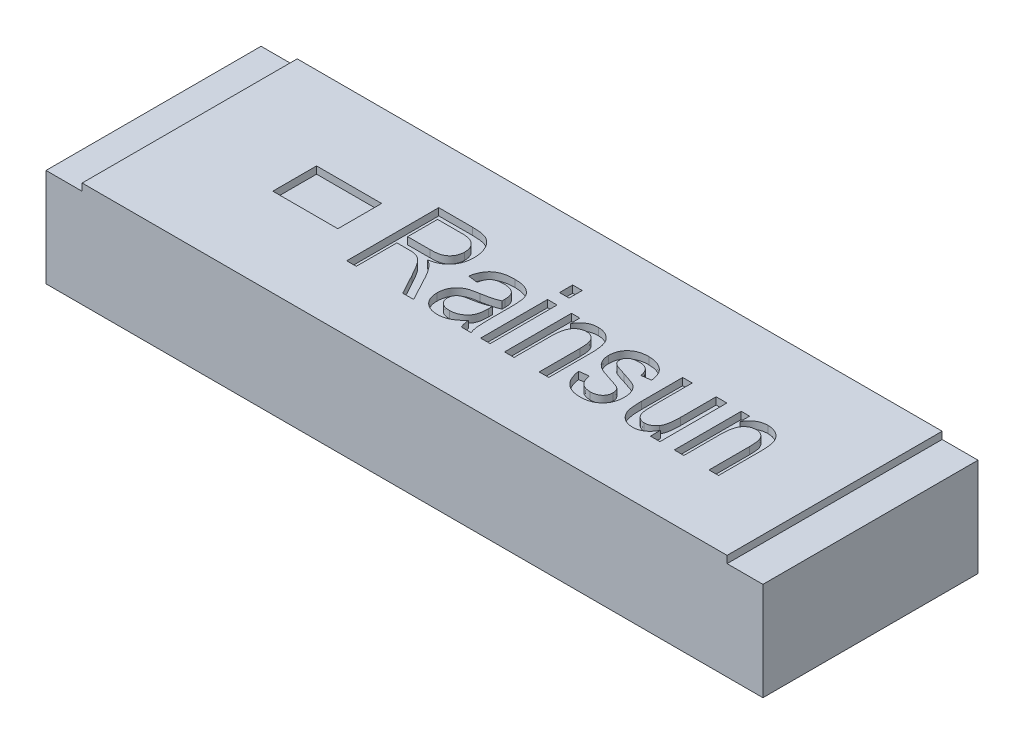
SolidWorks part; units mm, degrees
material "Plastique personnalisé"
ref_plane "Plan de face" through (0, 0, 0) normal (0, 0, 1) x (1, 0, 0)
ref_plane "Plan de dessus" through (0, 0, 0) normal (0, 1, 0) x (1, 0, 0)
ref_plane "Plan de droite" through (0, 0, 0) normal (1, 0, 0) x (0, 0, -1)
sketch "Esquisse1" plane through (0, 0, 0) normal (0, 1, 0) x (1, 0, 0)
  line L1 (-5, -1.5) -> (5, -1.5)
  line L2 (-5, -1.5) -> (-5, 1.5)
  line L3 (-5, 1.5) -> (5, 1.5)
  line L4 (5, -1.5) -> (5, 1.5)
  line L5 (-5, -1.5) -> (5, 1.5) construction
  line L6 (-5, 1.5) -> (5, -1.5) construction
  point P0 (0, 0)
  dimension "D1" = 10
  dimension "D2" = 3
extrude "Boss.-Extru.1" add sketch "Esquisse1" along normal blind 1.47
sketch "Esquisse2" plane through (0, 1.47, 0) normal (0, 1, 0) x (1, 0, 0)
  line L0 (0, 0) -> (-2.6139, 0.0364) construction
  line L2 (-3.0676, -0.2688) -> (-2.1603, -0.2688)
  line L3 (-3.0676, -0.2688) -> (-3.0676, 0.3417)
  line L4 (-3.0676, 0.3417) -> (-2.1603, 0.3417)
  line L5 (-2.1603, -0.2688) -> (-2.1603, 0.3417)
  line L6 (-3.0676, -0.2688) -> (-2.1603, 0.3417) construction
  line L7 (-3.0676, 0.3417) -> (-2.1603, -0.2688) construction
extrude "Enlèv. mat.-Extru.1" cut sketch "Esquisse2" against normal blind 0.1
sketch "Esquisse3" plane through (0, 1.47, 0) normal (0, 1, 0) x (1, 0, 0)
  line L0 (-5, -1.5) -> (5, -1.5) construction
  line L1 (-5, 1.5) -> (-4.4957, 1.5)
  line L2 (-5, 1.5) -> (-5, -1.5)
  line L3 (-5, -1.5) -> (-4.4957, -1.5)
  line L4 (-4.4957, 1.5) -> (-4.4957, -1.5)
  line L6 (5, 1.5) -> (4.5, 1.5)
  line L7 (5, 1.5) -> (5, -1.5)
  line L8 (5, -1.5) -> (4.5, -1.5)
  line L9 (4.5, 1.5) -> (4.5, -1.5)
extrude "Enlèv. mat.-Extru.2" cut sketch "Esquisse3" against normal blind 0.1
sketch "Esquisse4" plane through (0, 1.47, 0) normal (0, 1, 0) x (1, 0, 0)
  text T0 "Rainsun" font "Arial Narrow" height in points 5
extrude "Enlèv. mat.-Extru.3" cut sketch "Esquisse4" against normal blind 0.1
